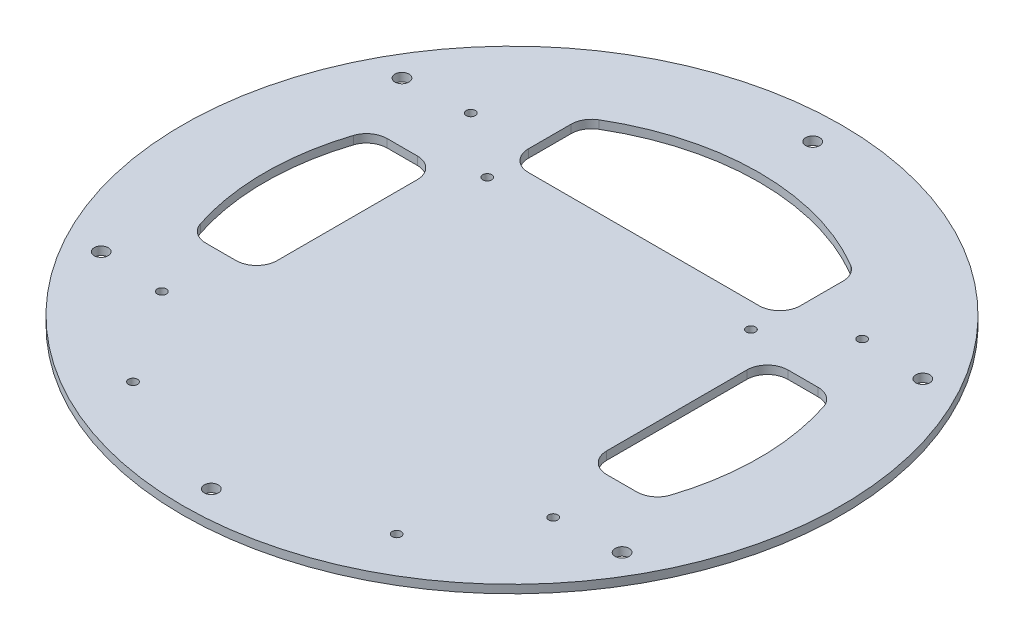
SolidWorks part; units mm, degrees
material "Thornel Mat VMA"
ref_plane "前视基准面" through (0, 0, 0) normal (0, 0, 1) x (1, 0, 0)
ref_plane "上视基准面" through (0, 0, 0) normal (0, 1, 0) x (1, 0, 0)
ref_plane "右视基准面" through (0, 0, 0) normal (1, 0, 0) x (0, 0, -1)
sketch "草图2" plane through (0, 0, 0) normal (0, 1, 0) x (1, 0, 0)
  circle A0 centre (0, 0) radius 80
  dimension "D1" = 160
extrude "凸台-拉伸1" add sketch "草图2" along normal blind 2
sketch "草图3" plane through (0, 0, 0) normal (0, -1, 0) x (1, 0, 0)
  line L0 (0, 0) -> (0, 17) construction
  line L1 (32, -26) -> (-32, -26) construction
  line L2 (32, -26) -> (32, 60) construction
  line L3 (32, 60) -> (-32, 60) construction
  line L4 (-32, -26) -> (-32, 60) construction
  line L5 (32, -26) -> (-32, 60) construction
  line L6 (32, 60) -> (-32, -26) construction
  line L8 (-47.5, -37.5) -> (47.5, -37.5) construction
  line L9 (-47.5, -37.5) -> (-47.5, 37.5) construction
  line L10 (-47.5, 37.5) -> (47.5, 37.5) construction
  line L11 (47.5, -37.5) -> (47.5, 37.5) construction
  line L12 (-47.5, -37.5) -> (47.5, 37.5) construction
  line L13 (-47.5, 37.5) -> (47.5, -37.5) construction
  circle A0 centre (32, 60) radius 1.1
  circle A1 centre (-32, 60) radius 1.1
  circle A2 centre (-32, -26) radius 1.1
  circle A4 centre (32, -26) radius 1.1
  circle A5 centre (-47.5, 37.5) radius 1.1
  circle A6 centre (47.5, 37.5) radius 1.1
  circle A7 centre (47.5, -37.5) radius 1.1
  circle A8 centre (-47.5, -37.5) radius 1.1
  point P0 (0, 17)
  dimension "D3" = 2.2
  dimension "D4" = 2.2
  dimension "D5" = 2.2
  dimension "D6" = 2.2
  dimension "D10" = 2.2
  dimension "D11" = 2.2
  dimension "D12" = 2.2
  dimension "D13" = 2.2
  dimension "D1" = 64
  dimension "D2" = 86
  dimension "D7" = 17
  dimension "D8" = 95
  dimension "D9" = 75
extrude "切除-拉伸1" cut sketch "草图3" against normal through all both and the other way through all
sketch "草图4" plane through (0, 2, 0) normal (0, 1, 0) x (1, 0, 0)
  line L0 (0, 0) -> (0, 60) construction
  line L1 (33, 47.3392) -> (33, 37)
  line L2 (28, 32) -> (-28, 32)
  line L3 (-33, 47.3392) -> (-33, 37)
  line L4 (0, 0) -> (-60, 0) construction
  line L5 (-52.3068, 22) -> (-45, 22)
  line L6 (-40, 17) -> (-40, -17)
  line L7 (-52.3068, -22) -> (-45, -22)
  line L8 (52.3068, -22) -> (45, -22)
  line L9 (40, 17) -> (40, -17)
  line L10 (52.3068, 22) -> (45, 22)
  arc A0 (-30.5455, 51.6428) -> (30.5455, 51.6428) centre (0, 0) cw
  arc A1 (33, 37) -> (28, 32) centre (28, 37) cw
  arc A2 (-33, 37) -> (-28, 32) centre (-28, 37) ccw
  arc A3 (-33, 47.3392) -> (-30.5455, 51.6428) centre (-28, 47.3392) cw
  arc A4 (30.5455, 51.6428) -> (33, 47.3392) centre (28, 47.3392) cw
  arc A5 (-57.0619, -18.5455) -> (-57.0619, 18.5455) centre (0, 0) cw
  arc A6 (-57.0619, 18.5455) -> (-52.3068, 22) centre (-52.3068, 17) cw
  arc A7 (-45, 22) -> (-40, 17) centre (-45, 17) cw
  arc A8 (-45, -22) -> (-40, -17) centre (-45, -17) ccw
  arc A9 (-52.3068, -22) -> (-57.0619, -18.5455) centre (-52.3068, -17) cw
  arc A10 (52.3068, -22) -> (57.0619, -18.5455) centre (52.3068, -17) ccw
  arc A11 (45, -22) -> (40, -17) centre (45, -17) cw
  arc A12 (45, 22) -> (40, 17) centre (45, 17) ccw
  arc A13 (57.0619, 18.5455) -> (52.3068, 22) centre (52.3068, 17) ccw
  arc A14 (57.0619, -18.5455) -> (57.0619, 18.5455) centre (0, 0) ccw
  point P7 (0, 32)
  point P10 (33, 32)
  point P13 (-33, 32)
  point P16 (-33, 50.1099)
  point P19 (33, 50.1099)
  point P25 (-40, 0)
  point P28 (-55.8211, 22)
  point P31 (-40, 22)
  point P34 (-40, -22)
  point P37 (-55.8211, -22)
  point P50 (55.8211, -22)
  point P51 (40, -22)
  point P52 (40, 22)
  point P53 (55.8211, 22)
  point P54 (40, 0)
  dimension "D1" = 5
  dimension "D4" = 60
  dimension "D5" = 60
  dimension "D8" = 5
  dimension "D2" = 32
  dimension "D3" = 33
  dimension "D6" = 40
  dimension "D7" = 22
extrude "切除-拉伸2" cut sketch "草图4" against normal through all
sketch "草图5" plane through (0, 2, 0) normal (0, 1, 0) x (1, 0, 0)
  line L0 (0, -73) -> (0, 0) construction
  circle A0 centre (0, -73) radius 1.7
  circle A7 centre (-63.2199, -36.5) radius 1.7
  circle A8 centre (-63.2199, 36.5) radius 1.7
  circle A9 centre (0, 73) radius 1.7
  circle A10 centre (63.2199, 36.5) radius 1.7
  circle A11 centre (63.2199, -36.5) radius 1.7
  dimension "D1" = 3.4
  dimension "D3" = 6
  dimension "D2" = 73
extrude "切除-拉伸3" cut sketch "草图5" against normal up to next
